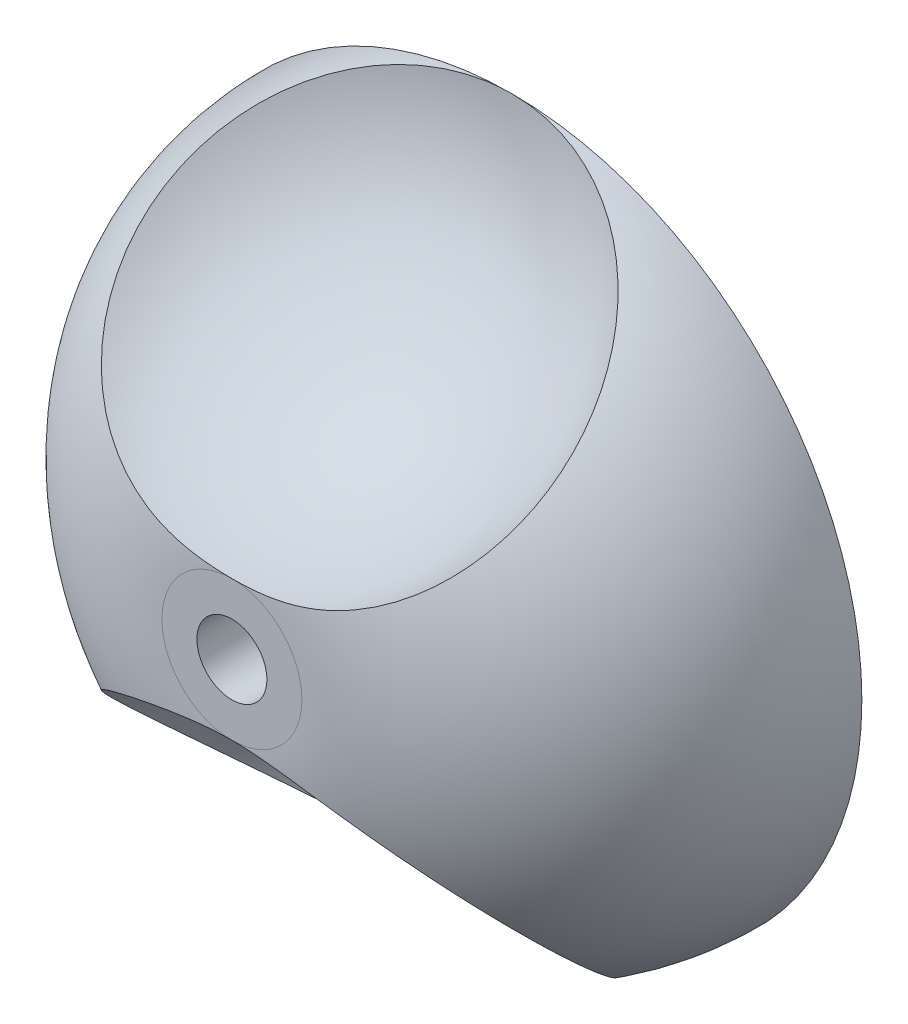
SolidWorks part; units mm, degrees
material "AISI 316 Stainless Steel Sheet (SS)"
ref_plane "Front Plane" through (0, 0, 0) normal (0, 0, 1) x (1, 0, 0)
ref_plane "Top Plane" through (0, 0, 0) normal (0, 1, 0) x (1, 0, 0)
ref_plane "Right Plane" through (0, 0, 0) normal (1, 0, 0) x (0, 0, -1)
sketch "Sketch1" plane through (0, 0, 0) normal (0, 0, 1) x (1, 0, 0)
  circle A0 centre (0, 0) radius 5
extrude "Boss-Extrude1" add sketch "Sketch1" along normal blind 4
fillet "Fillet1" radius 4 1 edges at (5, 0, 4)
sketch "Sketch2" plane through (0, 0, 0) normal (1, 0, 0) x (0, 0, -1)
  line L0 (-4, 1) -> (-4, -1) construction
  line L1 (0, -5) -> (0, 5) construction
  line L2 (0, 5) -> (-8, 5) construction
  line L3 (0, 5) -> (-8, 5)
  arc A0 (-8, 5) -> (0, 5) centre (-4, 5) ccw
revolve "Cut-Revolve2" cut sketch "Sketch2" angle 360 about L2
mirror "Mirror1" about plane through (0, 0, 0) normal (0, 1, 0) of "Cut-Revolve2"
sketch "Sketch3" plane through (0, 0, 0) normal (0, 0, -1) x (-1, 0, 0)
  circle A0 centre (0, 0) radius 0.5
extrude "Cut-Extrude1" cut sketch "Sketch3" against normal through all
